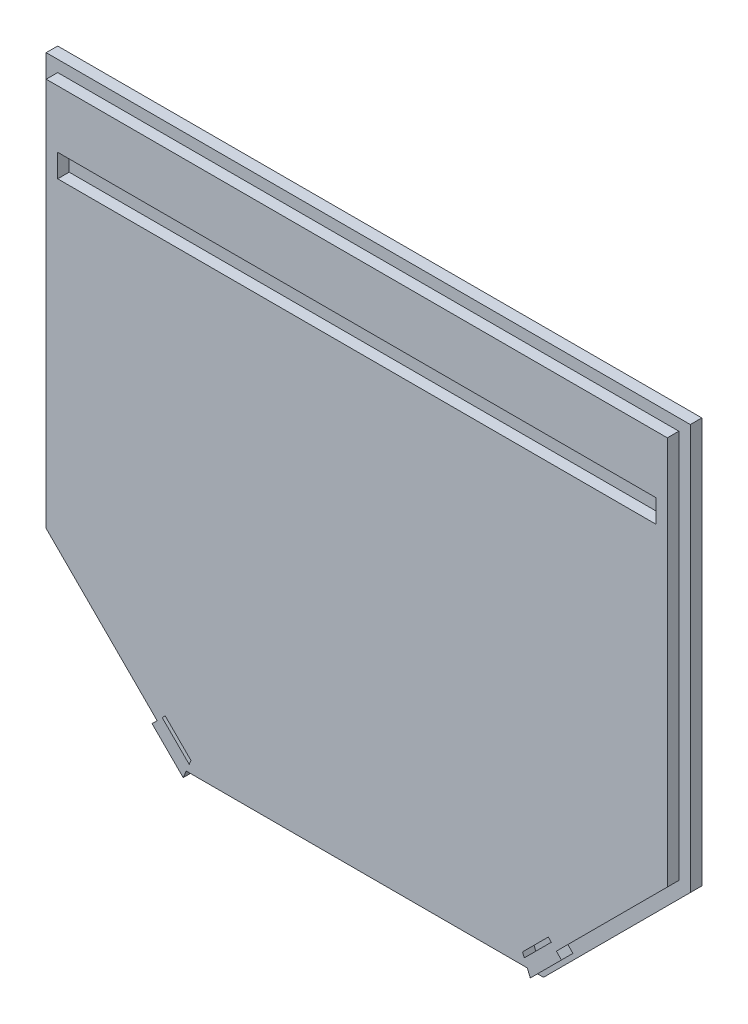
SolidWorks part; units mm, degrees
ref_plane "Front Plane" through (0, 0, 0) normal (0, 0, 1) x (1, 0, 0)
ref_plane "Top Plane" through (0, 0, 0) normal (0, 1, 0) x (1, 0, 0)
ref_plane "Right Plane" through (0, 0, 0) normal (1, 0, 0) x (0, 0, -1)
sketch "Sketch1" plane through (0, 0, 0) normal (0, 0, 1) x (1, 0, 0)
  line L0 (0, 0) -> (355.6, 0)
  line L1 (0, 0) -> (0, -223.774)
  line L2 (81.026, -304.8) -> (274.574, -304.8)
  line L3 (355.6, -223.774) -> (355.6, 0)
  line L4 (81.026, -304.8) -> (63.0655, -286.8395)
  line L5 (63.0655, -286.8395) -> (0, -223.774)
  line L6 (177.8, -304.8) -> (177.8, 0) construction
  line L7 (292.5345, -286.8395) -> (355.6, -223.774)
  line L8 (274.574, -304.8) -> (292.5345, -286.8395)
  dimension "D1" = 355.6
  dimension "D2" = 193.548
  dimension "D4" = 25.4
  dimension "D5" = 45
  dimension "D9" = 304.8
extrude "Boss-Extrude1" add sketch "Sketch1" along normal blind 12.7
sketch "Sketch2" plane through (0, 0, 12.7) normal (0, 0, 1) x (1, 0, 0)
  line L0 (6.35, -221.1437) -> (67.6075, -282.4012)
  line L1 (83.6563, -298.45) -> (271.9437, -298.45)
  line L2 (287.9925, -282.4012) -> (349.25, -221.1437)
  line L3 (349.25, -221.1437) -> (349.25, -6.35)
  line L4 (349.25, -6.35) -> (6.35, -6.35)
  line L5 (6.35, -6.35) -> (6.35, -221.1437)
  line L6 (0, -223.774) -> (81.026, -304.8) construction
  line L7 (81.026, -304.8) -> (274.574, -304.8) construction
  line L8 (274.574, -304.8) -> (355.6, -223.774) construction
  line L9 (355.6, -223.774) -> (355.6, 0) construction
  line L10 (0, 0) -> (0, -223.774) construction
  line L11 (355.6, 0) -> (0, 0) construction
  line L21 (81.026, -304.8) -> (83.6563, -298.45) construction
  line L23 (73.3233, -276.6854) -> (73.0994, -276.9093) construction
  line L24 (64.7877, -285.221) -> (82.0045, -302.4378)
  line L25 (82.0045, -302.4378) -> (83.6563, -298.45)
  line L26 (64.7877, -285.221) -> (67.6075, -282.4012)
  line L27 (0, 0) -> (0, -223.774)
  line L28 (0, -223.774) -> (81.026, -304.8)
  line L29 (81.026, -304.8) -> (274.574, -304.8)
  line L30 (274.574, -304.8) -> (355.6, -223.774)
  line L31 (355.6, -223.774) -> (355.6, 0)
  line L32 (355.6, 0) -> (0, 0)
  line L33 (177.8, -298.45) -> (177.8, 0) construction
  line L34 (12.7, -38.1) -> (342.9, -38.1)
  line L35 (12.7, -38.1) -> (12.7, -50.8)
  line L36 (12.7, -50.8) -> (342.9, -50.8)
  line L37 (342.9, -38.1) -> (342.9, -50.8)
  line L38 (273.5955, -302.4378) -> (271.9437, -298.45)
  line L39 (290.8123, -285.221) -> (273.5955, -302.4378)
  line L40 (290.8123, -285.221) -> (287.9925, -282.4012)
  line L41 (271.9437, -298.45) -> (349.25, -221.1437) construction
  line L42 (6.35, -221.1437) -> (83.6563, -298.45) construction
  line M13 (0, 0) -> (0, -223.774)
  line M14 (0, -223.774) -> (81.026, -304.8)
  line M15 (81.026, -304.8) -> (274.574, -304.8)
  line M16 (274.574, -304.8) -> (355.6, -223.774)
  line M17 (355.6, -223.774) -> (355.6, 0)
  line M18 (355.6, 0) -> (0, 0)
  dimension "D2" = 6.35
  dimension "D3" = 6.35
  dimension "D4" = 6.35
  dimension "D5" = 6.35
  dimension "D6" = 6.35
  dimension "D7" = 6.35
  dimension "D8" = 6.35
  dimension "D9" = 50.8
  dimension "D10" = 12.7
  dimension "D11" = 2.3622
extrude "Cut-Extrude1" cut sketch "Sketch2" against normal blind 6.35 contours L37 L34 L35 L36 | L5 L4 L3 L2 L1 L0 M18 M13 M14 M15 M16 M17 region at (177.8, -4.6835, 12.7) region at (177.8, -44.45, 12.7)
sketch "Sketch3" plane through (0, 0, 12.7) normal (0, 0, 1) x (1, 0, 0)
  line L0 (177.8, -304.8) -> (177.8, 0) construction
  line L1 (81.026, -304.8) -> (274.574, -304.8) construction
  line L2 (355.6, 0) -> (0, 0) construction
  line L3 (81.026, -304.8) -> (83.6563, -298.45) construction
  line L4 (85.3081, -294.4622) -> (70.4008, -279.555)
  line L5 (85.3081, -294.4622) -> (86.2865, -292.1)
  line L8 (70.4008, -279.555) -> (72.0712, -277.8846)
  line L9 (72.0712, -277.8846) -> (86.2865, -292.1)
  line L10 (285.1992, -279.555) -> (283.5288, -277.8846)
  line L11 (270.2919, -294.4622) -> (285.1992, -279.555)
  line L12 (270.2919, -294.4622) -> (269.3135, -292.1)
  line L13 (283.5288, -277.8846) -> (269.3135, -292.1)
  line L14 (11.7799, -215.7138) -> (6.35, -221.1437) construction
  line L15 (6.35, -221.1437) -> (67.6075, -282.4012) construction
  dimension "D1" = 21.082
  dimension "D2" = 3.9878
  dimension "D3" = 2.3622
  dimension "D4" = 90
  dimension "D5" = 67.5
extrude "Cut-Extrude3" cut sketch "Sketch3" against normal blind 6.35
